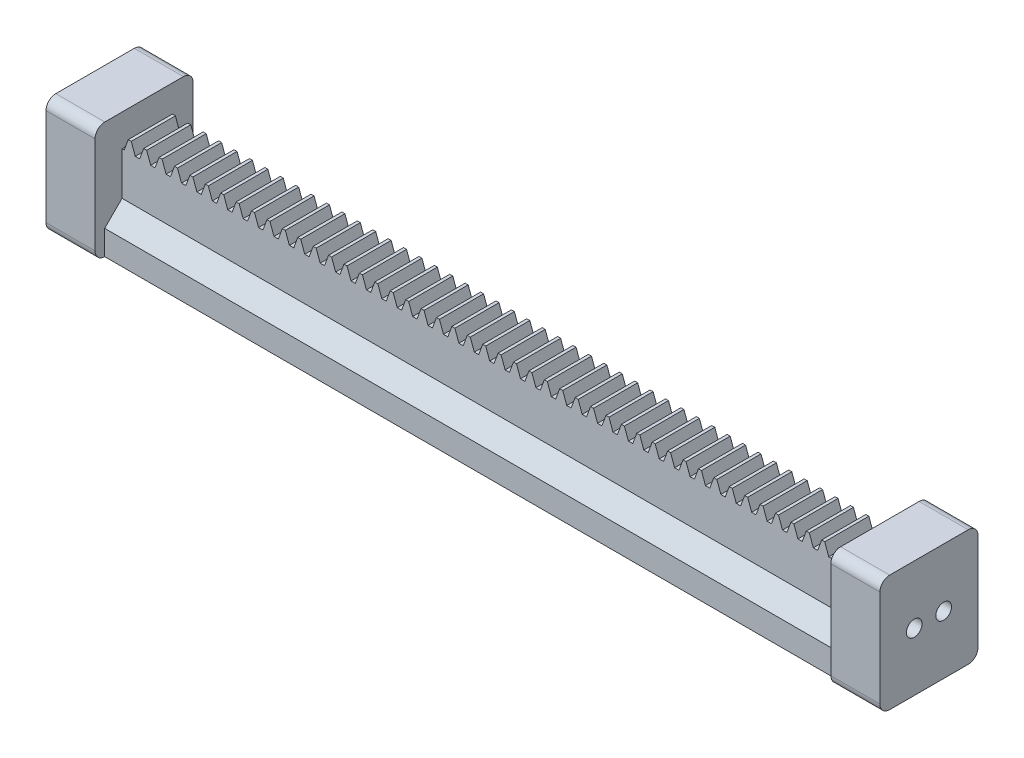
SolidWorks part; units mm, degrees
extrude "Blank" add sketch "BlankSke" against normal blind 9
sketch "BlankSke" plane through (0, 0, 0) normal (0, 0, 1) x (1, 0, 0)
  line L1 (0, 0) -> (150, 0)
  line L2 (0, 0) -> (0, 11)
  line L3 (0, 11) -> (150, 11)
  line L4 (150, 0) -> (150, 11)
  dimension "Length" = 150
ref_plane "Plane1" through (0, 0, 0) normal (0, 0, 1) x (1, 0, 0)
ref_plane "Plane2" through (0, 0, 0) normal (0, 1, 0) x (1, 0, 0)
ref_plane "Plane3" through (0, 0, 0) normal (1, 0, 0) x (0, 0, -1)
other "Configuration Table"
sketch "HoldingSke" plane through (0, 0, 0) normal (0, 1, 0) x (1, 0, 0)
  line L0 (0, 0) -> (0.1392, 0.9903)
  line L1 (-15, 0) -> (100, 0) construction
  line L2 (0, 0) -> (-2.1039, 2.3779)
  line L3 (0, 0) -> (-11.863, 4.5341)
  line L4 (0, 0) -> (5.6657, 6.5177)
  line L5 (0, 0) -> (-23.7986, -8.8762)
  line L6 (0, 0) -> (-10.5278, -7.1032)
  line L9 (-71.009, 38.7566) -> (69.9449, 90.0596)
  line L10 (-76.2, 3.3779) -> (-66.2, 3.3779)
  line L11 (0, 0) -> (-9, 0)
  line L12 (-76.2, 101.6) -> (-76.162, 101.6)
  line L13 (24.9733, 27.94) -> (52.9518, 28.4284)
  line L14 (24.9733, 27.94) -> (24.9743, 27.94)
  line L15 (24.9733, 27.94) -> (100.4006, 29.5858)
  circle A0 centre (0, 0) radius 19.05
  circle A1 centre (0, 0) radius 5
  circle A2 centre (0, 0) radius 12.7
  dimension "Num_teeth" = 49
  dimension "Width" = 9
  dimension "Length" = 150
  dimension "Pitch_height" = 10
sketch "TooCutSkeIll" plane through (0, 0, 0) normal (0, 0, 1) x (1, 0, 0)
  line L0 (-1.2538, 10.9737) -> (-0.5045, 8.9152)
  line L1 (-0.2687, 8.75) -> (0.2687, 8.75)
  line L2 (0.5045, 8.9152) -> (1.2538, 10.9737)
  line L3 (150, 11) -> (0, 11) construction
  line L4 (0, 0) -> (0, 64.897) construction
  line L5 (-13.208, 10) -> (12.954, 10) construction
  line L6 (0, 0) -> (150, 0) construction
  line L7 (0.8994, 10) -> (0.8994, 48.7463) construction
  line L8 (-0.8994, 10) -> (-0.8994, 48.7463) construction
  line L9 (1.2914, 11) -> (1.2914, 11.0254)
  line L10 (-1.2914, 11) -> (-1.2914, 11.0254)
  line L11 (-1.2914, 11.0254) -> (1.2914, 11.0254)
  arc A0 (0.2687, 8.75) -> (0.5045, 8.9152) centre (0.2687, 9.001) ccw
  arc A1 (-0.5045, 8.9152) -> (-0.2687, 8.75) centre (-0.2687, 9.001) ccw
  arc A2 (1.2914, 11) -> (1.2538, 10.9737) centre (1.2914, 10.96) ccw
  arc A3 (-1.2538, 10.9737) -> (-1.2914, 11) centre (-1.2914, 10.96) ccw
  dimension "Addendum_plus" = 1.0254
  dimension "Pitch_height" = 10
  dimension "Pressure_angle" = 20
  dimension "Gap_width" = 1.7988
  dimension "Dedendum" = 1.25
extrude "ToothCutIll" [suppressed] cut sketch "TooCutSkeIll" against normal through all
sketch "TooCutSkeSim" plane through (0, 0, 0) normal (0, 0, 1) x (1, 0, 0)
  line L0 (0.4444, 8.75) -> (-0.4444, 8.75)
  line L1 (1.2726, 11.0254) -> (0.4444, 8.75)
  line L2 (0, 17.4625) -> (0, 53.467) construction
  line L3 (1.2726, 11.0254) -> (-1.2726, 11.0254)
  line L6 (-1.2726, 11.0254) -> (-0.4444, 8.75)
  line L9 (-0.8994, 10) -> (0.8994, 10) construction
  line L10 (0, 0) -> (150, 0) construction
  line L11 (0.8994, 10) -> (0.8994, 53.467) construction
  line L12 (-0.8994, 10) -> (-0.8994, 53.467) construction
  dimension "Addendum_plus" = 1.0254
  dimension "Pitch_height" = 10
  dimension "Pressure_angle" = 20
  dimension "Gap_width" = 1.7988
  dimension "Dedendum" = 1.25
extrude "ToothCutSim" cut sketch "TooCutSkeSim" against normal through all
pattern_linear "TeethCuts" count 49 spacing 3.1416 along (1, 0, 0) of "ToothCutIll", "ToothCutSim"
ref_plane "Simetría" through (75, 0, 0) normal (1, 0, 0) x (0, 0, -1)
sketch "Sketch4" plane through (150, 0, 0) normal (1, 0, 0) x (0, 0, -1)
  line L0 (0, 0) -> (-3.5355, -3.5355)
  line L1 (0, 0) -> (0, 9.7171) construction
  line L2 (-3.5355, -3.5355) -> (-3.5355, -8.5355)
  line L3 (4.5, 11) -> (4.5, 0) construction
  line L4 (9, 11) -> (0, 11) construction
  line L5 (9, 0) -> (0, 0) construction
  line L6 (12.5355, -3.5355) -> (12.5355, -8.5355)
  line L7 (9, 0) -> (12.5355, -3.5355)
  line L8 (12.5355, -8.5355) -> (-3.5355, -8.5355)
  line L9 (9, 0) -> (0, 0)
  dimension "D1" = 5
  dimension "D2" = 45
  dimension "D3" = 5
extrude "Boss-Extrude4" add sketch "Sketch4" against normal through all
sketch "Sketch5" plane through (150, 0, 0) normal (1, 0, 0) x (0, 0, -1)
  line L0 (12.5, -8.5355) -> (-3.5, -8.5355)
  line L1 (12.5355, -8.5355) -> (-3.5355, -8.5355) construction
  line L2 (12.5355, -8.5355) -> (12.5355, 11) construction
  line L3 (12.5355, 11) -> (-3.5355, 11) construction
  line L4 (-3.5355, -8.5355) -> (-3.5355, 11) construction
  line L6 (-5.5, -6.5355) -> (-5.5, 13.2322)
  line L7 (-3.5, 15.2322) -> (12.5, 15.2322)
  line L8 (14.5, -6.5355) -> (14.5, 13.2322)
  line L9 (-5.5, -12.7678) -> (14.5, 15.2322) construction
  line L10 (-5.5, 15.2322) -> (14.5, -12.7678) construction
  arc A0 (-3.5, 15.2322) -> (-5.5, 13.2322) centre (-3.5, 13.2322) ccw
  arc A1 (12.5, 15.2322) -> (14.5, 13.2322) centre (12.5, 13.2322) cw
  arc A2 (14.5, -6.5355) -> (12.5, -8.5355) centre (12.5, -6.5355) cw
  arc A3 (-3.5, -8.5355) -> (-5.5, -6.5355) centre (-3.5, -6.5355) cw
  point P4 (4.5, 1.2322)
  dimension "D3" = 2
  dimension "D1" = 28
  dimension "D2" = 20
extrude "Boss-Extrude5" add sketch "Sketch5" along normal blind 10
mirror "Mirror2" about plane through (75, 0, 0) normal (1, 0, 0) of "Boss-Extrude5"
sketch "Sketch6" plane through (160, 0, 0) normal (1, 0, 0) x (0, 0, -1)
  line L0 (1.5, 3.3483) -> (7.5, 3.3483) construction
  circle A0 centre (1.5, 3.3483) radius 1.6
  circle A1 centre (7.5, 3.3483) radius 1.6
  point P3 (4.5, 3.3483)
  dimension "D1" = 3.2
  dimension "D2" = 3.2
  dimension "D3" = 3
extrude "Cut-Extrude1" cut sketch "Sketch6" against normal up to surface (10 mm away) up to face at (150, 2.7983, -4.5)
ref_plane "Plane4" through (0, 0, 0) normal (1, 0, 0) x (0, 0, -1)
split "Split1" trim tools "Plane4" bodies to split 110 resulting bodies 111 112
equation "' \"Module@HoldingSke\" = 6.35"
equation "' \"Num_teeth@HoldingSke\" = 12"
equation "' \"Ap@HoldingSke\" =  20"
equation "' \"Ap@HoldingSke\" = 20"
equation "' \"Width@HoldingSke\" = 0.25 * 25.4"
equation "' \"Show_teeth@HoldingSke\" = 500"
equation "' \"Backlash@HoldingSke\" = 0.009 * 25.4"
equation "' \"Addendum_fac@HoldingSke\" = 1.0"
equation "' \"Dedendum_fac@HoldingSke\" = 1.25"
equation "' \"Dedendum_add@HoldingSke\" = 0.00005 * 25.4"
equation "' \"Clearance_fac@HoldingSke\" = 0.25"
equation "' \"Pitch_height@HoldingSke\" = 1 * 25.4"
equation "' \"Length@HoldingSke\" = 4.71 * 25.4"
equation "\"Pitch@HoldingSke\" = 1 / \"Module@HoldingSke\""
equation "\"MPH@HoldingSke\" = \"Dedendum_fac@HoldingSke\" / \"Pitch@HoldingSke\" + 2 * \"Dedendum_add@HoldingSke\" + 0.002 * 25.4"
equation "\"MPH@HoldingSke\" = ((sgn( \"MPH@HoldingSke\" - \"Pitch_height@HoldingSke\")+1)*( \"MPH@HoldingSke\" - \"Pitch_height@HoldingSke\"))/2 + \"Pitch_height@HoldingSke\""
equation "\"Blank_height@BlankSke\" = \"Pitch_height@HoldingSke\" + \"Addendum_fac@HoldingSke\"  / \"Pitch@HoldingSke\" "
equation "\"Length@BlankSke\" =  \"Length@HoldingSke\""
equation "\"Pressure_angle@TooCutSkeIll\" = \"Ap@HoldingSke\""
equation "\"Addendum_plus@TooCutSkeIll\" =  \"Addendum_fac@HoldingSke\"  / \"Pitch@HoldingSke\" + 0.001 *25.4"
equation "\"Dedendum@TooCutSkeIll\" = \"Dedendum_fac@HoldingSke\"  / \"Pitch@HoldingSke\""
equation "\"Pitch_height@TooCutSkeIll\" =  \"MPH@HoldingSke\""
equation "\"Gap_width@TooCutSkeIll\" = 3.14159265 / 2 / \"Pitch@HoldingSke\" + 6 * \"Backlash@HoldingSke\""
equation "\"Pressure_angle@TooCutSkeSim\" = \"Ap@HoldingSke\""
equation "\"Addendum_plus@TooCutSkeSim\" =  \"Addendum_fac@HoldingSke\"  / \"Pitch@HoldingSke\" + 0.001 * 25.4"
equation "\"Dedendum@TooCutSkeSim\" = \"Dedendum_fac@HoldingSke\"  / \"Pitch@HoldingSke\""
equation "\"Pitch_height@TooCutSkeSim\" =  \"MPH@HoldingSke\""
equation "\"Gap_width@TooCutSkeSim\" = 3.14159265 / 2 / \"Pitch@HoldingSke\" + 6 * \"Backlash@HoldingSke\""
equation "\"Root_fillet@TooCutSkeIll\" = \"Clearance_fac@HoldingSke\" / \"Pitch@HoldingSke\" + \"Dedendum_add@HoldingSke\""
equation "\"Break_rad@TooCutSkeIll\" = 0.02 / \"Pitch@HoldingSke\" * 2"
equation "\"Linear_pitch@TeethCuts\" = 3.14159265 / \"Pitch@HoldingSke\""
equation "\"Num_teeth@HoldingSke\" = int( ( \"Length@HoldingSke\" + 0 ) / (3.14159265 / \"Pitch@HoldingSke\")) + 0.9999  + 1"
equation " \"Num_teeth@TeethCuts\" = int( \"Show_teeth@HoldingSke\" ) + 1"
equation " \"Num_teeth@TeethCuts\" = ((sgn( \"Num_teeth@TeethCuts\" - \"Num_teeth@HoldingSke\" )-1)*( \"Num_teeth@TeethCuts\" - \"Num_teeth@HoldingSke\" ))/-2+ \"Num_teeth@HoldingSke\""
equation " \"Num_teeth@TeethCuts\" = ((sgn( \"Num_teeth@TeethCuts\" - 2.0)+1)*( \"Num_teeth@TeethCuts\" - 2.0))/2 +2.0"
